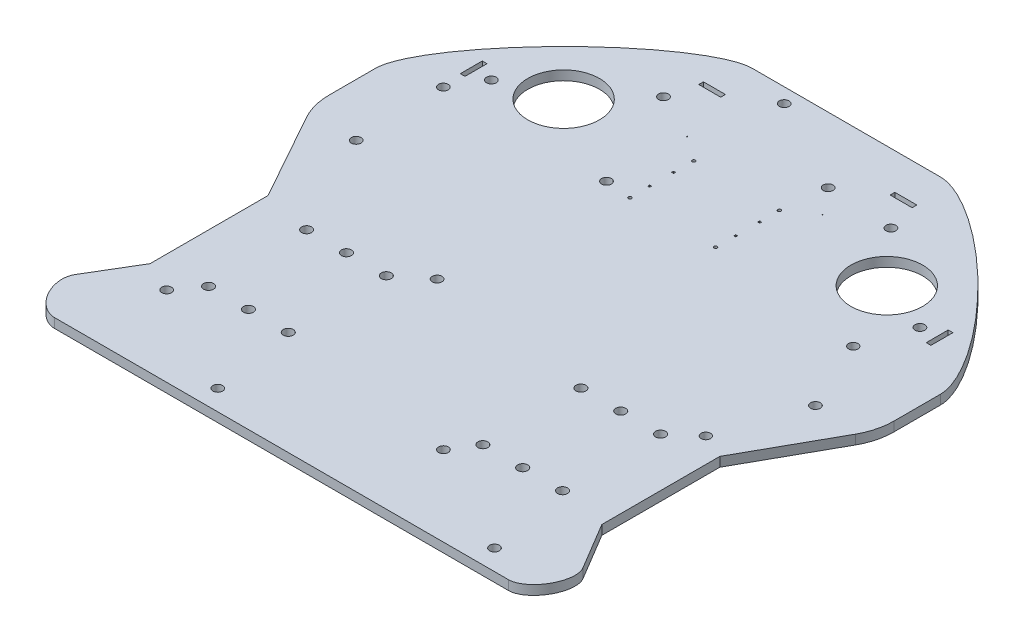
SolidWorks part; units mm, degrees
ref_plane "Front Plane" through (0, 0, 0) normal (0, 0, 1) x (1, 0, 0)
ref_plane "Top Plane" through (0, 0, 0) normal (0, 1, 0) x (1, 0, 0)
ref_plane "Right Plane" through (0, 0, 0) normal (1, 0, 0) x (0, 0, -1)
sketch "Sketch1" plane through (0, 0, 0) normal (0, 1, 0) x (1, 0, 0)
  line L0 (-90, 180) -> (-90, 0) construction
  line L1 (-180, 180) -> (0, 180)
  line L2 (-180, 180) -> (-180, 0)
  line L3 (-180, 0) -> (0, 0)
  line L4 (0, 180) -> (0, 0)
  line L5 (-180, 90) -> (0, 90) construction
  line L6 (-180, 30) -> (0, 30)
  line L7 (-130, 30) -> (-50, 30)
  line L8 (-130, 30) -> (-130, -30)
  line L9 (-130, -30) -> (-50, -30)
  line L10 (-50, 30) -> (-50, -30)
  line L11 (-130, 30) -> (-50, -30) construction
  line L12 (-130, -30) -> (-50, 30) construction
  dimension "D1" = 180
  dimension "D2" = 180
  dimension "D3" = 60
  dimension "D4" = 80
extrude "Boss-Extrude1" add sketch "Sketch1" along normal blind 3 contours L10 L3 L8 L9 | L2 L6 L4 L1 | L6 L10 L3 L4 | L8 L6 L2 L3 | L10 L6 L8 L3 region at (-90, 0, -105) region at (-155, 0, -15) region at (-25, 0, -15) region at (-90, 0, -15) region at (-90, 0, 15)
sketch "Sketch2" plane through (0, 3, 0) normal (0, 1, 0) x (1, 0, 0)
  line L0 (-180, 30) -> (0, 30)
  line L1 (-180, 180) -> (-180, 0) construction
  line L2 (0, 180) -> (0, 0) construction
  line L3 (-180, 180) -> (0, 180) construction
  line L4 (-90, 180) -> (-90, -30) construction
  line L5 (-130, -30) -> (-50, -30) construction
  dimension "D1" = 150
sketch "Sketch3" plane through (0, 3, 0) normal (0, 1, 0) x (1, 0, 0)
  line L0 (-180, 122) -> (0, 122)
  line L1 (-180, 180) -> (-180, 0) construction
  line L2 (0, 180) -> (0, 0) construction
  line L3 (-180, 30) -> (0, 30) construction
  dimension "D1" = 92
sketch "Sketch5" plane through (0, 3, 0) normal (0, 1, 0) x (1, 0, 0)
  line L0 (-114, 180) -> (-114, -30)
  line L1 (-180, 180) -> (0, 180) construction
  line L2 (-130, -30) -> (-50, -30) construction
  line L3 (-90, 180) -> (-90, -30) construction
  dimension "D1" = 24
fillet "Fillet1" radius 60 2 edges at (0, 1.5, -180) (-180, 1.5, -180) conic rho 0.2
sketch "Sketch6" plane through (0, 3, 0) normal (0, 1, 0) x (1, 0, 0)
  line L0 (-50, 0) -> (-130, 0)
  line L1 (-130, 0) -> (-130, -30)
  line L2 (-130, -30) -> (-50, -30)
  line L3 (-50, -30) -> (-50, 0)
  line L4 (-180, 0) -> (-162, 30.1113)
  line L5 (-162, 30.1113) -> (-162, 67.7113)
  line L6 (-162, 67.7113) -> (-180, 100)
  line L7 (-180, 120) -> (-180, 0) construction
  line L8 (-90, 180) -> (-90, -30) construction
  line L10 (-90, 180) -> (-90, 0) construction
  line L11 (0, 0) -> (-18, 30.1113)
  line L12 (-18, 30.1113) -> (-18, 67.7113)
  line L13 (-18, 67.7113) -> (0, 100)
  line M3 (0, 0) -> (0, 120)
  line M7 (-180, 120) -> (-180, 0)
  line M9 (-130, 0) -> (-130, -30)
  line M10 (-130, -30) -> (-50, -30)
  line M11 (-50, -30) -> (-50, 0)
  dimension "D1" = 37.6
  dimension "D2" = 72
  dimension "D3" = 100
extrude "Cut-Extrude1" cut sketch "Sketch6" against normal blind 10 contours L0 M11 M9 M10 | L5 L6 L4 M7 | L13 L12 L11 M3 region at (-90, 3, 15) region at (-172.3605, 3, -49.5379) region at (-7.6395, 3, -49.5379)
fillet "Fillet2" radius 10 2 edges at (-180, 1.5, 0) (0, 1.5, 0) conic rho 0.25
fillet "Fillet3" radius 20 2 edges at (-180, 1.5, -100) (0, 1.5, -100)
sketch "Sketch8" plane through (0, 3, 0) normal (0, 1, 0) x (1, 0, 0)
  line L1 (-63, 168.5) -> (-56, 168.5)
  line L2 (-63, 168.5) -> (-63, 167)
  line L3 (-63, 167) -> (-56, 167)
  line L4 (-56, 168.5) -> (-56, 167)
  line L5 (-117, 168.5) -> (-124, 168.5)
  line L6 (-117, 168.5) -> (-117, 167)
  line L7 (-117, 167) -> (-124, 167)
  line L8 (-124, 168.5) -> (-124, 167)
  line L9 (-165, 139) -> (-163.5, 139)
  line L10 (-165, 139) -> (-165, 132)
  line L11 (-165, 132) -> (-163.5, 132)
  line L12 (-163.5, 139) -> (-163.5, 132)
  line L13 (-16.5, 139) -> (-15, 139)
  line L14 (-16.5, 139) -> (-16.5, 132)
  line L15 (-16.5, 132) -> (-15, 132)
  line L16 (-15, 139) -> (-15, 132)
  circle A4 centre (-105.105, 175.3311) radius 1.55
  circle A5 centre (-74.9002, 159.1312) radius 1.55
  circle A6 centre (-141.5, 141.43) radius 11.43
  circle A7 centre (-38.5, 141.43) radius 11.43
  circle A8 centre (-112, 125.592) radius 1.55
  circle A9 centre (-164, 125.592) radius 1.55
  circle A10 centre (-112, 71.592) radius 1.55
  circle A11 centre (-146.4125, 64.417) radius 1.5875
  circle A12 centre (-133.7125, 64.417) radius 1.5875
  circle A13 centre (-121.0125, 64.417) radius 1.5875
  circle A14 centre (-146.4125, 33.175) radius 1.5875
  circle A15 centre (-133.7125, 33.175) radius 1.5875
  circle A16 centre (-121.0125, 33.175) radius 1.5875
  circle A17 centre (-58.9875, 64.417) radius 1.5875
  circle A18 centre (-46.2875, 64.417) radius 1.5875
  circle A19 centre (-33.5875, 64.417) radius 1.5875
  circle A20 centre (-33.5875, 33.175) radius 1.5875
  circle A21 centre (-46.2875, 33.175) radius 1.5875
  circle A22 centre (-58.9875, 33.175) radius 1.5875
  circle A23 centre (-63.9, 25.5) radius 1.55
  circle A24 centre (-28.6, 6.5) radius 1.55
  circle A25 centre (-116.8, 6.5) radius 1.55
  circle A26 centre (-152.1, 25.5) radius 1.55
  circle A27 centre (-27.14, 119.392) radius 1.5
  circle A28 centre (-25.87, 71.132) radius 1.5
  dimension "D1" = 22.86
  dimension "D2" = 22.86
  dimension "D3" = 3.1
  dimension "D4" = 3.1
  dimension "D5" = 3.1
  dimension "D6" = 3.1
  dimension "D7" = 3.1
  dimension "D8" = 3.175
  dimension "D9" = 3.175
  dimension "D10" = 3.175
  dimension "D11" = 3.175
  dimension "D12" = 3.175
  dimension "D13" = 3.175
  dimension "D14" = 3.1
  dimension "D15" = 3.1
  dimension "D16" = 3.1
  dimension "D17" = 3.1
  dimension "D18" = 3.175
  dimension "D19" = 3.175
  dimension "D20" = 3.175
  dimension "D21" = 3.175
  dimension "D22" = 3.175
  dimension "D23" = 3.175
  dimension "D24" = 3
  dimension "D25" = 3
extrude "Cut-Extrude2" cut sketch "Sketch8" against normal up to next (3 mm away)
sketch "Sketch9" plane through (0, 0, 0) normal (0, -1, 0) x (1, 0, 0)
  line L1 (-68.18, -150.89) -> (-68.42, -150.89)
  line L2 (-68.18, -150.89) -> (-68.18, -150.65)
  line L3 (-68.18, -150.65) -> (-68.42, -150.65)
  line L4 (-68.42, -150.89) -> (-68.42, -150.65)
  line L5 (-111.36, -150.89) -> (-111.6, -150.89)
  line L6 (-111.36, -150.89) -> (-111.36, -150.65)
  line L7 (-111.36, -150.65) -> (-111.6, -150.65)
  line L8 (-111.6, -150.89) -> (-111.6, -150.65)
  line L9 (-76.01, -139.0625) -> (-76.645, -139.0625)
  line L10 (-76.01, -139.0625) -> (-76.01, -138.4275)
  line L11 (-76.01, -138.4275) -> (-76.645, -138.4275)
  line L12 (-76.645, -139.0625) -> (-76.645, -138.4275)
  line L13 (-76.01, -131.4425) -> (-76.645, -131.4425)
  line L14 (-76.01, -131.4425) -> (-76.01, -130.8075)
  line L15 (-76.01, -130.8075) -> (-76.645, -130.8075)
  line L16 (-76.645, -131.4425) -> (-76.645, -130.8075)
  line L17 (-103.47, -139.0625) -> (-104.105, -139.0625)
  line L18 (-103.47, -139.0625) -> (-103.47, -138.4275)
  line L19 (-103.47, -138.4275) -> (-104.105, -138.4275)
  line L20 (-104.105, -139.0625) -> (-104.105, -138.4275)
  line L21 (-103.47, -131.4425) -> (-104.105, -131.4425)
  line L22 (-103.47, -131.4425) -> (-103.47, -130.8075)
  line L23 (-103.47, -130.8075) -> (-104.105, -130.8075)
  line L24 (-104.105, -131.4425) -> (-104.105, -130.8075)
  circle A0 centre (-163.2, -97) radius 1.55
  circle A1 centre (-158.3, -135.2) radius 1.55
  circle A2 centre (-126.25, -158) radius 1.55
  circle A3 centre (-53.75, -158) radius 1.55
  circle A4 centre (-21.7, -135.2) radius 1.55
  circle A5 centre (-16.8, -97) radius 1.55
  circle A6 centre (-76.405, -124.775) radius 0.5
  circle A7 centre (-103.71, -145.095) radius 0.5
  circle A8 centre (-76.405, -145.095) radius 0.5
  circle A9 centre (-103.71, -124.775) radius 0.5
  dimension "D1" = 3.1
  dimension "D2" = 3.1
  dimension "D3" = 3.1
  dimension "D4" = 3.1
  dimension "D5" = 3.1
  dimension "D6" = 3.1
  dimension "D7" = 1
  dimension "D8" = 1
  dimension "D9" = 1
  dimension "D10" = 1
extrude "Cut-Extrude3" cut sketch "Sketch9" against normal up to next
